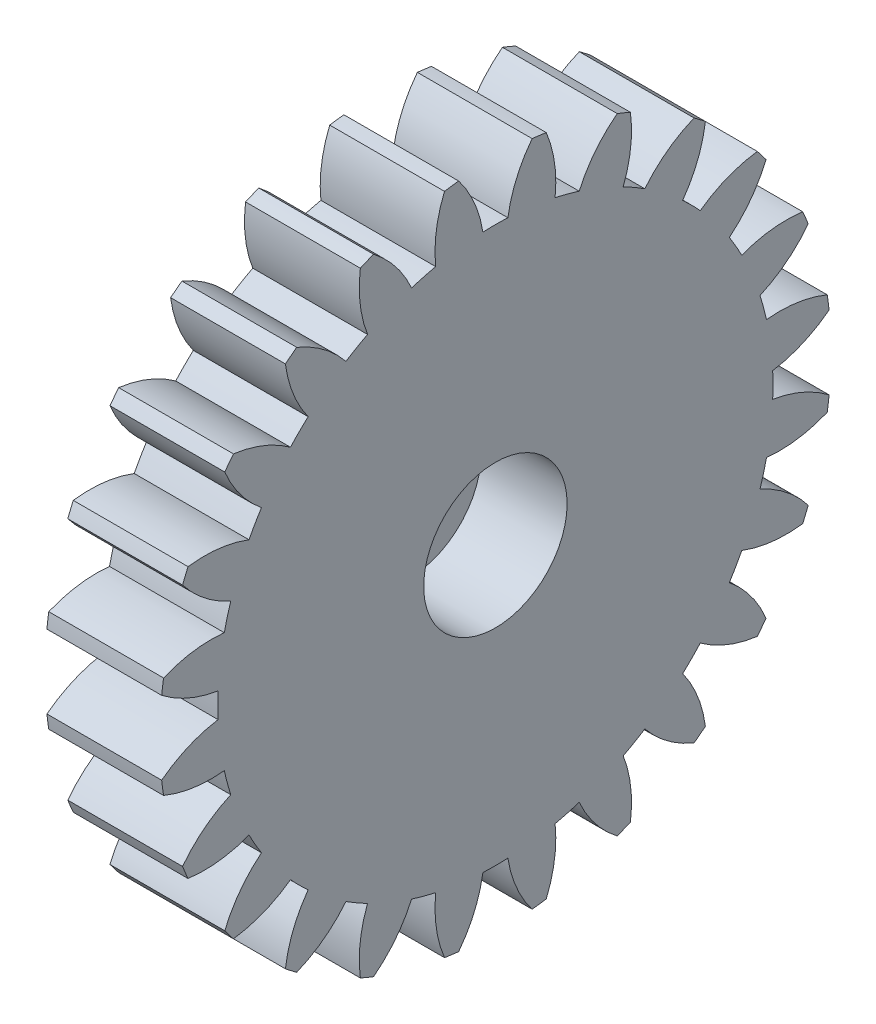
SolidWorks part; units mm, degrees
ref_plane "Plane1" through (0, 0, 0) normal (0, 0, 1) x (1, 0, 0)
ref_plane "Plane2" through (0, 0, 0) normal (0, 1, 0) x (1, 0, 0)
ref_plane "Plane3" through (0, 0, 0) normal (1, 0, 0) x (0, 0, -1)
other "Configuration Table"
sketch "HoldingSke" plane through (0, 0, 0) normal (0, 1, 0) x (1, 0, 0)
  line L0 (0, 0) -> (1.0151, -0.4519)
  line L1 (-15, 0) -> (100, 0) construction
  line L2 (0, 0) -> (-2.1039, 2.3779)
  line L3 (0, 0) -> (-11.863, 4.5341)
  line L4 (0, 0) -> (7.8894, 3.5126)
  line L5 (0, 0) -> (-46.8476, -17.4728)
  line L6 (0, 0) -> (-3.3159, -2.2372)
  line L7 (-2.1039, 2.3779) -> (8.6586, 51.2059)
  line L8 (-76.2, 54.61) -> (-75.9, 54.61)
  line L9 (-71.009, 38.7566) -> (-53.1078, 45.2721)
  line L10 (-76.2, 71.12) -> (104.1128, 71.12)
  line L11 (0, 0) -> (-4, 0)
  line L12 (-76.2, 101.6) -> (-76.166, 101.6)
  line L13 (24.9733, 27.94) -> (52.9518, 28.4284)
  line L14 (24.9733, 27.94) -> (24.9743, 27.94)
  line L15 (24.9733, 27.94) -> (100.4006, 29.5858)
  line L16 (-63.627, -0.9) -> (-12.827, -0.9)
  circle A0 centre (0, 0) radius 1
  circle A1 centre (0, 0) radius 9.674
  circle A2 centre (0, 0) radius 37.5
  circle A3 centre (0, 0) radius 1
  dimension "Num_teeth" = 24
  dimension "Pitch_radius" = 180.3128
  dimension "Width" = 4
  dimension "Thickness" = 4
sketch "BasProSke" plane through (0, 0, 0) normal (0, 1, 0) x (1, 0, 0)
  line L0 (-10, 0) -> (60, 0) construction
  line L1 (0, 0) -> (0, 11.7)
  line L2 (0, 0) -> (4, 0)
  line L3 (4, 0) -> (4, 11.7)
  line L4 (4, 11.7) -> (0, 11.7)
  dimension "Thickness" = 4
  dimension "Diameter" = 23.4
revolve "Base-Revolve" add sketch "BasProSke" angle 360 about L0
sketch "TooCutSke" plane through (0, 0, 0) normal (1, 0, 0) x (0, 0, -1)
  line L1 (0, 0) -> (0, 107) construction
  line L2 (0, 0) -> (-0.7658, 10.7728) construction
  line L3 (0, 0) -> (-2.8143, 21.3768) construction
  line L4 (-0.7658, 10.7728) -> (-1.4072, 10.6884) construction
  arc A0 (0.4348, 9.6642) -> (-0.4348, 9.6642) centre (0, 0) ccw
  arc A1 (1.2983, 11.6533) -> (-1.2983, 11.6533) centre (0, 0) ccw
  circle A2 centre (0, 0) radius 10.8 construction
  circle A3 centre (0, 0) radius 10.1487 construction
  arc A4 (-0.4348, 9.6642) -> (-1.2983, 11.6533) centre (-4.7024, 8.9935) ccw
  arc A5 (1.2983, 11.6533) -> (0.4348, 9.6642) centre (4.7024, 8.9935) ccw
extrude "ToothCut" cut sketch "TooCutSke" along normal through all
fillet "Breaks" [suppressed] radius 0.018 tangent propagation no
fillet "RootFillets" [suppressed] radius 0.226
pattern_circular "TeethCuts" count 24 every 15 about axis through (-10, 0, 0) along (1, 0, 0) of "ToothCut", "RootFillets", "Breaks"
sketch "HubNeaOneSke" plane through (0, 0, 0) normal (-1, 0, 0) x (0, 0, 1)
  circle A0 centre (0, 0) radius 9.674
  dimension "Diameter" = 19.348
extrude "HubNearOne" [suppressed] add sketch "HubNeaOneSke" along normal blind 46.0001
sketch "HubNeaBotSke" plane through (0, 0, 0) normal (-1, 0, 0) x (0, 0, 1)
  circle A0 centre (0, 0) radius 9.674
  dimension "Diameter" = 19.348
extrude "HubNearBoth" [suppressed] add sketch "HubNeaBotSke" along normal blind 23
ref_plane "FarPln" through (4, 0, 0) normal (1, 0, 0) x (0, 0, -1)
sketch "HubFarSke" plane through (4, 0, 0) normal (1, 0, 0) x (0, 0, -1)
  circle A0 centre (0, 0) radius 9.674
  dimension "Diameter" = 19.348
extrude "HubFar" [suppressed] add sketch "HubFarSke" along normal blind 23
sketch "BorSke" plane through (0, 0, 0) normal (1, 0, 0) x (0, 0, -1)
  circle A0 centre (0, 0) radius 1
  dimension "Diameter" = 2
extrude "Bore" cut sketch "BorSke" along normal mid plane 100.0001
sketch "KeySke" plane through (0, 0, 0) normal (1, 0, 0) x (0, 0, -1)
  line L0 (-0.4, 0) -> (-0.4, 1.3)
  line L1 (-0.4, 1.3) -> (0.4, 1.3)
  line L2 (0.4, 1.3) -> (0.4, 0)
  line L3 (0, 0) -> (0, 34) construction
  line L4 (-0.4, 0) -> (0.4, 0)
  dimension "Width" = 0.8
extrude "Keyway" [suppressed] cut sketch "KeySke" along normal mid plane 100.0001
pattern_circular "Keyway2" [suppressed] count 2 every 90 about axis through (-10, 0, 0) along (1, 0, 0) reverse direction yes
sketch "Sketch1" plane through (4, 0, 0) normal (1, 0, 0) x (0, 0, -1)
  circle A0 centre (0, 0) radius 2.5
extrude "Cut-Extrude1" cut sketch "Sketch1" against normal blind 3
equation "' \"Module@HoldingSke\" = 6.35"
equation "' \"Num_teeth@HoldingSke\" = 12"
equation "' \"Ap@HoldingSke\" =  20"
equation "' \"Ap@HoldingSke\" = 20"
equation "' \"Width@HoldingSke\" = 0.5 * 25.4"
equation "' \"Hub_dia@HoldingSke\"= 1 * 25.4"
equation "' \"Hub_dia@HoldingSke\" = 1 * 25.4"
equation "' \"Overall_len@HoldingSke\" = 1.0 * 25.4"
equation "' \"Bore@HoldingSke\" = 0.75 * 25.4"
equation "' \"T_dim@HoldingSke\" = 0.1 * 25.4"
equation "' \"Width@KeySke\" = 0.25 * 25.4"
equation "' \"Show_teeth@HoldingSke\" = 13"
equation "' \"Backlash@HoldingSke\" = 0.009 * 25.4"
equation "' \"Addendum_fac@HoldingSke\" = 1.0"
equation "' \"Dedendum_fac@HoldingSke\" = 1.25"
equation "' \"Dedendum_add@HoldingSke\" = 0.00005 * 25.4"
equation "' \"Clearance_fac@HoldingSke\" = 0.25"
equation "\"Pitch@HoldingSke\" = 1 / \"Module@HoldingSke\""
equation "\"Overcut_dia@TooCutSke\" = (\"Num_teeth@HoldingSke\" + 2 * \"Addendum_fac@HoldingSke\") / \"Pitch@HoldingSke\" + 0.002 * 25.4"
equation "\"Pitch_dia@TooCutSke\" = \"Num_teeth@HoldingSke\" / \"Pitch@HoldingSke\""
equation "\"Base_dia@TooCutSke\" = \"Num_teeth@HoldingSke\" / \"Pitch@HoldingSke\" * cos((\"Ap@HoldingSke\"  * 3.14159265 / 180))"
equation "\"Root_dia@TooCutSke\" = (\"Num_teeth@HoldingSke\" + 2) / \"Pitch@HoldingSke\" - 2 * (\"Addendum_fac@HoldingSke\" + \"Dedendum_fac@HoldingSke\") / \"Pitch@HoldingSke\" - \"Dedendum_add@HoldingSke\" * 2"
equation "\"Half_ang@TooCutSke\" = 180 / \"Num_teeth@HoldingSke\""
equation "\"Half_CT@TooCutSke\" = \"Num_teeth@HoldingSke\" / \"Pitch@HoldingSke\" * sin((3.14159265 / 2 / \"Num_teeth@HoldingSke\")) / 2 - 7 * \"Backlash@HoldingSke\" / 4"
equation "\"Flank_rad@TooCutSke\" = \"Num_teeth@HoldingSke\" / \"Pitch@HoldingSke\" / 5"
equation "\"Radius@RootFillets\" = \"Clearance_fac@HoldingSke\" / \"Pitch@HoldingSke\" + \"Dedendum_add@HoldingSke\""
equation "\"Break_rad@Breaks\" = 0.02 / \"Pitch@HoldingSke\""
equation "\"Thickness@HoldingSke\" = \"Width@HoldingSke\""
equation "\"OAL@HoldingSke\" = \"Thickness@HoldingSke\""
equation "\"MHD@HoldingSke\" = (\"Num_teeth@HoldingSke\" + 2) / \"Pitch@HoldingSke\" - 2 * (\"Addendum_fac@HoldingSke\" + \"Dedendum_fac@HoldingSke\")  / \"Pitch@HoldingSke\" - \"Dedendum_add@HoldingSke\" * 2"
equation "\"MBD@HoldingSke\" = (\"Num_teeth@HoldingSke\" + 2) / \"Pitch@HoldingSke\" - 2 * (\"Addendum_fac@HoldingSke\" + \"Dedendum_fac@HoldingSke\")  / \"Pitch@HoldingSke\" - \"Dedendum_add@HoldingSke\" * 2 - 0.002 * 25.4"
equation "\"MHD@HoldingSke\" = ((sgn( \"MHD@HoldingSke\" - \"Hub_dia@HoldingSke\" )-1)*( \"MHD@HoldingSke\" - \"Hub_dia@HoldingSke\" ))/-2+ \"Hub_dia@HoldingSke\""
equation "\"MBD@HoldingSke\" = ((sgn( \"MBD@HoldingSke\" - \"Bore@HoldingSke\" )-1)*( \"MBD@HoldingSke\" - \"Bore@HoldingSke\" ))/-2+ \"Bore@HoldingSke\""
equation "\"OAL@HoldingSke\" = ((sgn( \"OAL@HoldingSke\" - \"Overall_len@HoldingSke\" )+1)*( \"OAL@HoldingSke\" - \"Overall_len@HoldingSke\" ))/2 + \"Overall_len@HoldingSke\" + 0.000002 * 25.4"
equation "\"Num_teeth@TeethCuts\" = int( \"Show_teeth@HoldingSke\" ) + 1"
equation "\"Num_teeth@TeethCuts\" = ((sgn( \"Num_teeth@TeethCuts\" - \"Num_teeth@HoldingSke\" )-1)*( \"Num_teeth@TeethCuts\" - \"Num_teeth@HoldingSke\" ))/-2+ \"Num_teeth@HoldingSke\""
equation "\"Num_teeth@TeethCuts\" = ((sgn( \"Num_teeth@TeethCuts\" - 2.0)+1)*( \"Num_teeth@TeethCuts\" - 2.0))/2 +2.0"
equation "\"Angle@TeethCuts\" = 360.0 / \"Num_teeth@HoldingSke\""
equation "\"Diameter@BasProSke\" = (\"Num_teeth@HoldingSke\" + 2 * \"Addendum_fac@HoldingSke\") / \"Pitch@HoldingSke\""
equation "\"Thickness@BasProSke\"  = \"Thickness@HoldingSke\""
equation "' \"Fillet_rad@BasProSke\" =  \"Thickness@HoldingSke\" * 0.05"
equation "' \"Fillet_rad@BasProSke\" = \"Thickness@HoldingSke\" * 0.05"
equation "\"MHD@HoldingSke\" = ((sgn( \"MHD@HoldingSke\" - \"Root_dia@TooCutSke\" )-1)*( \"MHD@HoldingSke\" - \"Root_dia@TooCutSke\" ))/-2+ \"Root_dia@TooCutSke\""
equation "\"Diameter@HubNeaOneSke\" = \"MHD@HoldingSke\""
equation "\"Length@HubNearOne\" = \"OAL@HoldingSke\" - \"Thickness@BasProSke\""
equation "\"Diameter@HubNeaBotSke\" = \"MHD@HoldingSke\""
equation "\"Length@HubNearBoth\" = ( \"OAL@HoldingSke\" - \"Thickness@BasProSke\" ) / 2.0"
equation "\"Thickness@FarPln\" = \"Thickness@BasProSke\""
equation "\"Diameter@HubFarSke\" = \"MHD@HoldingSke\""
equation "\"Length@HubFar\" = ( \"OAL@HoldingSke\" - \"Thickness@BasProSke\" ) / 2.0"
equation "\"Diameter@BorSke\" = \"MBD@HoldingSke\""
equation "\"D1@Bore\" = \"OAL@HoldingSke\" * 2.0"
equation "\"D1@Keyway\" = \"OAL@HoldingSke\" * 2.0"
equation "\"Offset@KeySke\" = \"T_dim@HoldingSke\" + \"MBD@HoldingSke\" / 2.0"
